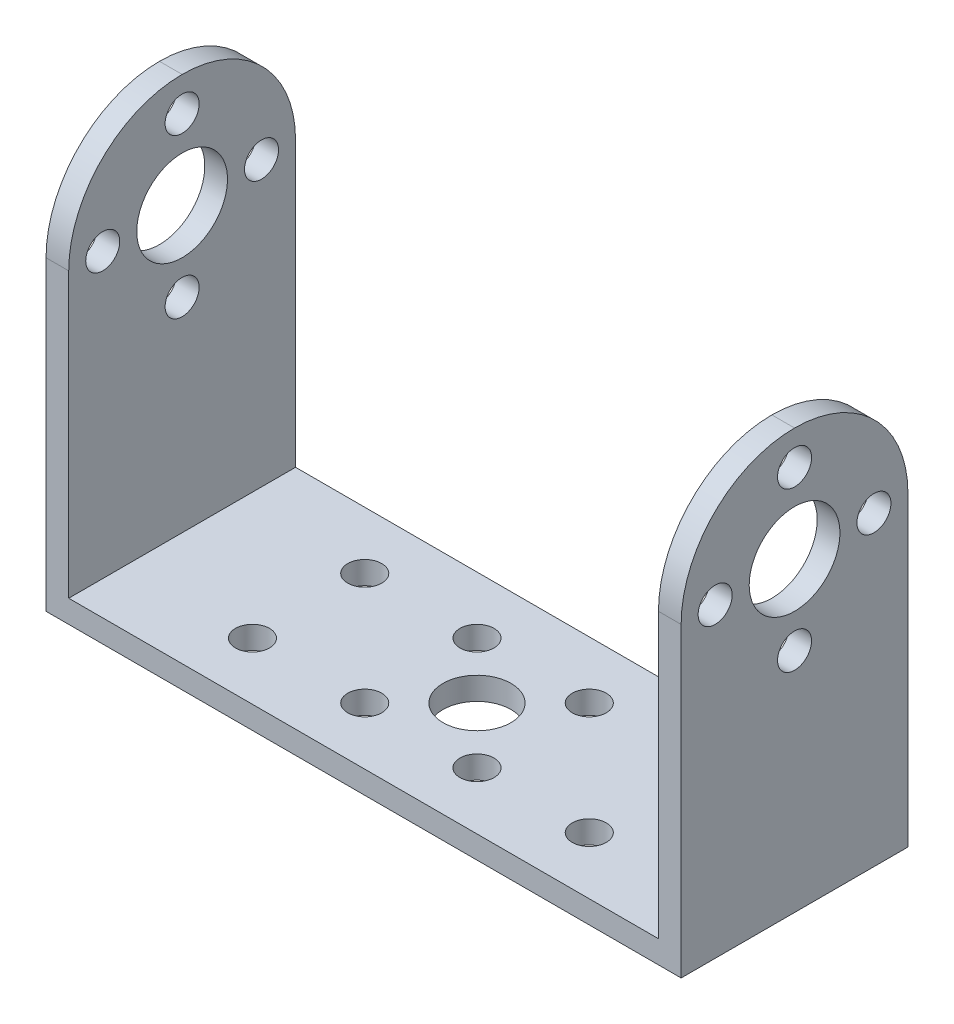
SolidWorks part; units mm, degrees
ref_plane "前视基准面" through (0, 0, 0) normal (0, 0, 1) x (1, 0, 0)
ref_plane "上视基准面" through (0, 0, 0) normal (0, 1, 0) x (1, 0, 0)
ref_plane "右视基准面" through (0, 0, 0) normal (1, 0, 0) x (0, 0, -1)
other "Configuration Table"
sketch "草图1" plane through (0, 0, 0) normal (0, 0, 1) x (1, 0, 0)
  line L0 (0, 0) -> (56, 0)
  line L1 (56, 0) -> (56, 37)
  line L2 (0, 0) -> (0, 37)
  dimension "D1" = 37
  dimension "D2" = 56
extrude "拉伸-薄壁1" add sketch "草图1" along normal blind 20 thin thin type one direction wall 2
fillet "圆角1" radius 10 4 edges at (55, 37, 20) (55, 37, 0) (1, 37, 0) (1, 37, 20)
sketch "草图2" plane through (0, 0, 0) normal (-1, 0, 0) x (0, 0, 1)
  line L0 (0, 27) -> (20, 27) construction
  circle A1 centre (10, 34) radius 1.5
  circle A2 centre (17, 27) radius 1.5
  circle A3 centre (10, 20) radius 1.5
  circle A4 centre (3, 27) radius 1.5
  circle A5 centre (10, 27) radius 4
  point P17 (10, 27)
  dimension "D1" = 8
  dimension "D2" = 3
  dimension "D3" = 4
extrude "切除-拉伸1" cut sketch "草图2" against normal through all
sketch "草图3" plane through (0, 0, 0) normal (0, -1, 0) x (1, 0, 0)
  line L0 (28, 20) -> (28, 0) construction
  line L1 (56, 20) -> (0, 20) construction
  line L2 (56, 0) -> (0, 0) construction
  circle A0 centre (28, 10) radius 3
  circle A1 centre (32.9495, 14.9495) radius 1.5
  circle A2 centre (23.0505, 14.9495) radius 1.5
  circle A3 centre (23.0505, 5.0505) radius 1.5
  circle A4 centre (32.9495, 5.0505) radius 1.5
  circle A5 centre (42.8485, 14.9495) radius 1.5
  circle A6 centre (42.8485, 5.0505) radius 1.5
  circle A7 centre (13.1515, 5.0505) radius 1.5
  circle A8 centre (13.1515, 14.9495) radius 1.5
  dimension "D1" = 6
  dimension "D4" = 3
  dimension "D5" = 3
  dimension "D6" = 3
  dimension "D7" = 3
  dimension "D10" = 3
  dimension "D11" = 3
  dimension "D2" = 9.899
  dimension "D3" = 9.899
  dimension "D8" = 9.899
  dimension "D9" = 9.899
extrude "切除-拉伸2" cut sketch "草图3" against normal through all
